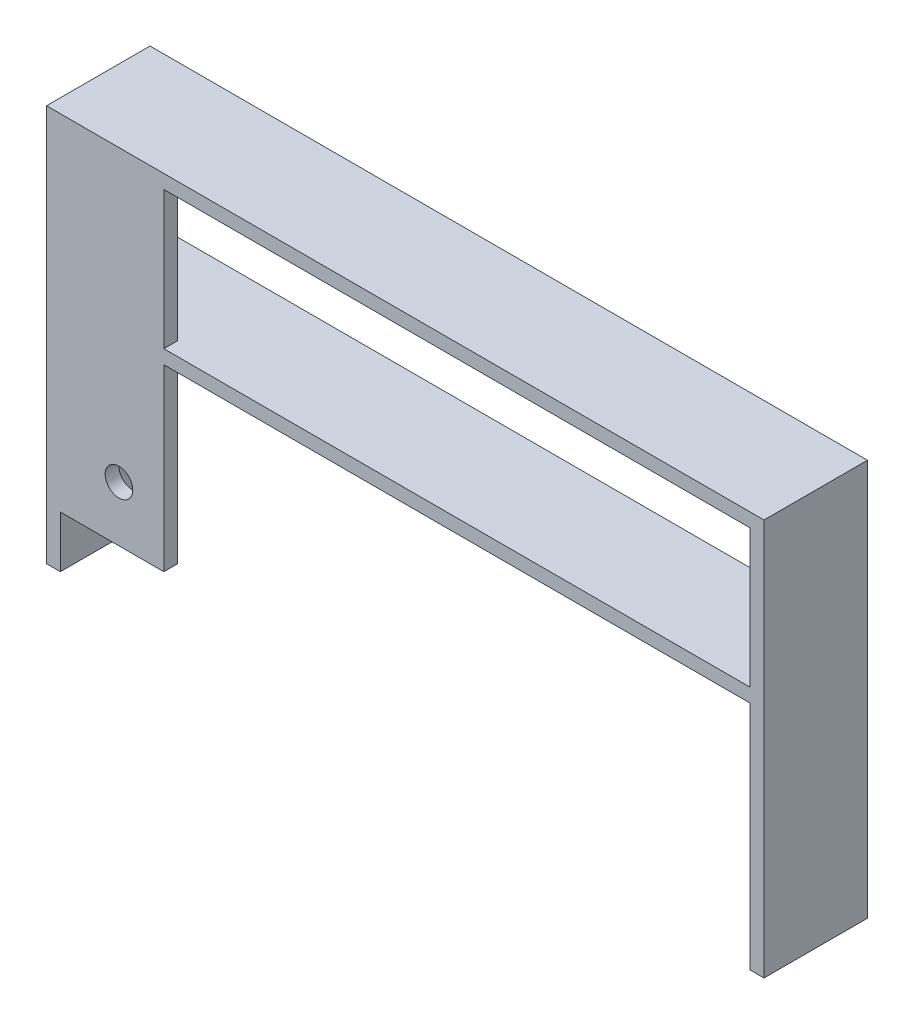
SolidWorks part; units mm, degrees
ref_plane "Front Plane" through (0, 0, 0) normal (0, 0, 1) x (1, 0, 0)
ref_plane "Top Plane" through (0, 0, 0) normal (0, 1, 0) x (1, 0, 0)
ref_plane "Right Plane" through (0, 0, 0) normal (1, 0, 0) x (0, 0, -1)
sketch "Sketch1" plane through (0, 0, 0) normal (0, 0, 1) x (1, 0, 0)
  line L0 (0, 0) -> (0, 33.5)
  line L1 (0, 55.5) -> (100, 55.5)
  line L2 (100, 55.5) -> (100, 35.5)
  line L3 (-2, 0) -> (-2, 57.5)
  line L4 (-2, 57.5) -> (102, 57.5)
  line L5 (102, 57.5) -> (102, 0)
  line L6 (-2, 0) -> (0, 0)
  line L7 (100, 0) -> (102, 0)
  line L8 (0, 35.5) -> (100, 35.5)
  line L9 (0, 33.5) -> (100, 33.5)
  line L10 (100, 33.5) -> (100, 0)
  line L11 (0, 35.5) -> (0, 55.5)
  line L12 (100, 55.5) -> (100, 0) construction
  line L14 (0, 0) -> (0, 55.5) construction
  dimension "D1" = 55.5
  dimension "D2" = 100
  dimension "D4" = 20
  dimension "D3" = 2
  dimension "D5" = 2
extrude "Boss-Extrude1" add sketch "Sketch1" along normal blind 15
sketch "Sketch2" plane through (0, 0, 15) normal (0, 0, -1) x (-1, 0, 0)
  line L0 (-100, 55.5) -> (0, 55.5) construction
  line L1 (0, 55.5) -> (-15, 55.5)
  line L2 (0, 55.5) -> (0, 35.5)
  line L3 (0, 35.5) -> (-15, 35.5)
  line L4 (-15, 55.5) -> (-15, 35.5)
  dimension "D1" = 15
extrude "Boss-Extrude2" add sketch "Sketch2" along normal blind 2
sketch "Sketch3" plane through (0, 0, 15) normal (0, 0, 1) x (1, 0, 0)
  line L0 (15, 55.5) -> (15, 35.5) construction
  line L1 (0, 33.5) -> (15, 33.5)
  line L2 (0, 33.5) -> (0, 7.5)
  line L3 (0, 7.5) -> (15, 7.5)
  line L4 (15, 33.5) -> (15, 7.5)
  dimension "D1" = 26
extrude "Boss-Extrude3" add sketch "Sketch3" against normal blind 2
sketch "Sketch4" plane through (0, 0, 13) normal (0, 0, -1) x (-1, 0, 0)
  line L0 (-15, 33.5) -> (0, 33.5) construction
  line L1 (-15, 7.5) -> (-15, 33.5) construction
  circle A0 centre (-8.5, 15.5) radius 2
  dimension "D1" = 4
  dimension "D2" = 18
  dimension "D3" = 6.5
extrude "Cut-Extrude1" cut sketch "Sketch4" against normal up to next
